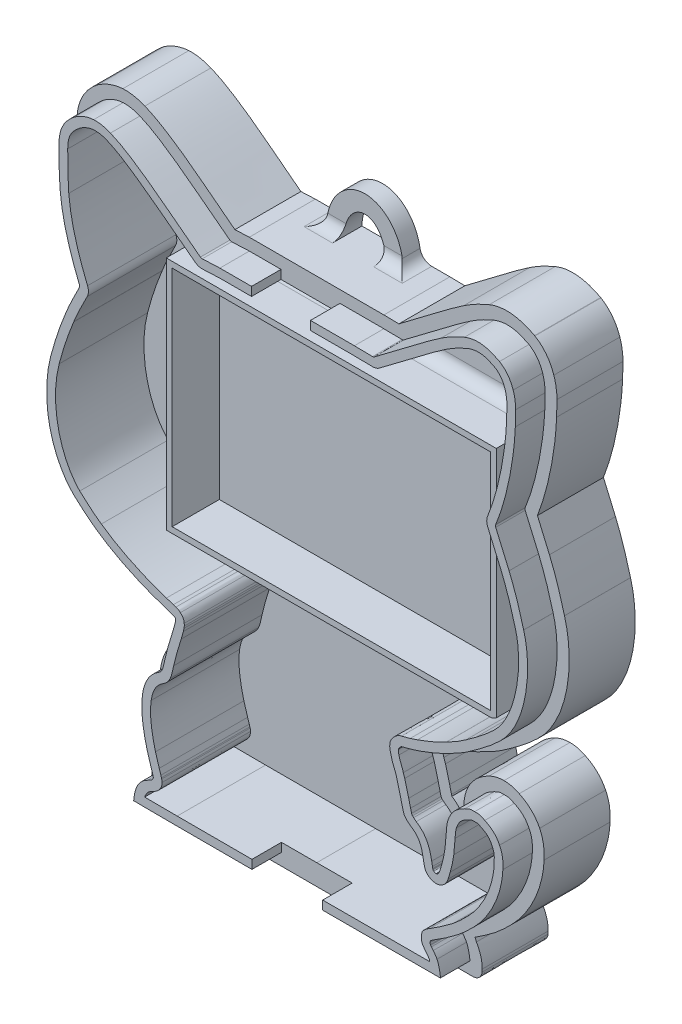
SolidWorks part; units mm, degrees
ref_plane "Front" through (0, 0, 0) normal (0, 0, 1) x (1, 0, 0)
ref_plane "Top" through (0, 0, 0) normal (0, 1, 0) x (1, 0, 0)
ref_plane "Right" through (0, 0, 0) normal (1, 0, 0) x (0, 0, -1)
sketch "Mech_Outlines_Dog" plane through (0, 0, 0) normal (0, 0, 1) x (1, 0, 0)
  line L1 (74.9398, 0.9126) -> (48.9706, 0.8869)
  line L7 (71.492, 32.5287) -> (70.2527, 32.1324)
  line L14 (63.42, 86.4697) -> (60.3508, 86.5232)
  line L15 (60.3508, 86.5232) -> (48.9353, 86.5232)
  line L16 (48.9353, 86.5232) -> (37.5273, 86.5232)
  line L17 (37.5273, 86.5232) -> (34.5339, 86.3884)
  line L22 (73.1431, 2.4109) -> (48.9672, 2.3716)
  line L27 (71.0247, 33.949) -> (69.8274, 33.5656)
  line L32 (63.3944, 84.986) -> (60.338, 85.0395)
  line L33 (60.338, 85.0395) -> (48.9354, 85.0395)
  line L34 (48.9354, 85.0395) -> (37.5613, 85.0395)
  line L35 (37.5613, 85.0395) -> (34.6011, 84.9061)
  line L40 (75.4762, -1.1182) -> (49.0458, -1.1447)
  line L42 (77.0346, 0.7654) -> (77.0108, 0.3114)
  line L48 (60.3548, 88.5576) -> (62.8985, 88.5136)
  line L51 (37.5165, 88.5576) -> (60.3548, 88.5576)
  line L53 (35.0717, 88.4472) -> (37.5165, 88.5576)
  line L56 (34.5113, 86.8831) -> (37.5166, 87.0182)
  line L57 (37.5166, 87.0182) -> (48.9356, 87.0182)
  line L58 (48.9356, 87.0182) -> (60.3546, 87.0182)
  line L59 (60.3546, 87.0182) -> (63.4286, 86.965)
  line L62 (70.4053, 31.6632) -> (71.6522, 32.0554)
  line L63 (75.4324, 0.8747) -> (75.3997, 0.419)
  line L64 (75.3997, 0.419) -> (48.9694, 0.3927)
  spline S0 degree 3 poles (16.1085, 97.6224) (15.1263, 97.5645) (14.0794, 97.2279) (12.9032, 96.4251) knots 0 0 0 0 1 1 1 1
  spline S1 degree 3 poles (12.9032, 96.4251) (10.8702, 94.8674) (10.2573, 93.2137) (10.2274, 91.1494) knots 0 0 0 0 1 1 1 1
  spline S2 degree 3 poles (10.2274, 91.1494) (10.1937, 88.8245) (10.2902, 85.9514) (10.4089, 84.5626) knots 0 0 0 0 1 1 1 1
  spline S3 degree 3 poles (10.4089, 84.5626) (10.8046, 79.9338) (12.2076, 75.8345) (13.7003, 72.1489) knots 0 0 0 0 1 1 1 1
  spline S4 degree 3 poles (13.7003, 72.1489) (13.7533, 72.018) (13.7479, 71.8706) (13.6854, 71.744) knots 0 0 0 0 1 1 1 1
  spline S5 degree 3 poles (13.6854, 71.744) (12.8695, 70.0922) (12.0156, 68.4848) (11.3692, 66.8103) knots 0 0 0 0 1 1 1 1
  spline S6 degree 3 poles (11.3692, 66.8103) (11.3675, 66.8062) (11.3657, 66.8022) (11.3638, 66.7981) knots 0 0 0 0 1 1 1 1
  spline S7 degree 3 poles (11.3638, 66.7981) (10.3632, 64.3951) (9.5104, 61.8412) (8.8174, 59.1813) knots 0 0 0 0 1 1 1 1
  spline S8 degree 3 poles (8.8174, 59.1813) (7.136, 52.6817) (8.6138, 44.9032) (12.7203, 40.814) knots 0 0 0 0 1 1 1 1
  spline S9 degree 3 poles (12.7203, 40.814) (13.8839, 39.7054) (15.1708, 38.6412) (16.5528, 37.6527) knots 0 0 0 0 1 1 1 1
  spline S10 degree 3 poles (16.5528, 37.6527) (19.588, 35.4818) (23.8433, 33.4143) (28.0129, 32.0933) knots 0 0 0 0 1 1 1 1
  spline S11 degree 3 poles (28.0129, 32.0933) (28.4457, 31.9562) (28.8478, 31.8228) (29.152, 31.7174) knots 0 0 0 0 1 1 1 1
  spline S12 degree 3 poles (29.152, 31.7174) (29.3041, 31.6647) (29.4314, 31.6193) (29.5293, 31.582) knots 0 0 0 0 1 1 1 1
  spline S13 degree 3 poles (29.5293, 31.582) (29.6997, 31.528) (29.7592, 31.4685) (29.8367, 31.4215) knots 0 0 0 0 1 1 1 1
  spline S14 degree 3 poles (29.8367, 31.4215) (30.0145, 31.2642) (29.9977, 31.1577) (30.0053, 31.0998) knots 0 0 0 0 1 1 1 1
  spline S15 degree 3 poles (30.0053, 31.0998) (30.013, 31.0418) (30.011, 31.008) (30.0094, 30.9765) knots 0 0 0 0 1 1 1 1
  spline S16 degree 3 poles (30.0094, 30.9765) (30.0062, 30.9135) (29.9984, 30.8639) (29.9884, 30.8065) knots 0 0 0 0 1 1 1 1
  spline S17 degree 3 poles (29.9884, 30.8065) (29.9685, 30.6918) (29.938, 30.5555) (29.897, 30.3921) knots 0 0 0 0 1 1 1 1
  spline S18 degree 3 poles (29.897, 30.3921) (29.815, 30.0653) (29.6927, 29.6377) (29.5475, 29.1758) knots 0 0 0 0 1 1 1 1
  spline S19 degree 3 poles (29.5475, 29.1758) (28.8677, 27.0124) (28.5655, 25.9343) (28.2351, 24.4934) knots 0 0 0 0 1 1 1 1
  spline S20 degree 3 poles (28.2351, 24.4934) (27.9956, 23.449) (27.9088, 22.9752) (27.7373, 22.5937) knots 0 0 0 0 1 1 1 1
  spline S21 degree 3 poles (27.7373, 22.5937) (27.6515, 22.403) (27.5225, 22.233) (27.3845, 22.1142) knots 0 0 0 0 1 1 1 1
  spline S22 degree 3 poles (27.3845, 22.1142) (27.2464, 21.9955) (27.1173, 21.9196) (26.9591, 21.8122) knots 0 0 0 0 1 1 1 1
  spline S23 degree 3 poles (26.9591, 21.8122) (25.5697, 20.8686) (24.7237, 19.4316) (24.4067, 17.4) knots 0 0 0 0 1 1 1 1
  spline S24 degree 3 poles (24.4067, 17.4) (24.0896, 15.3685) (24.3311, 12.7525) (25.1692, 9.5949) knots 0 0 0 0 1 1 1 1
  spline S25 degree 3 poles (25.1692, 9.5949) (25.3317, 8.9826) (25.6352, 7.9761) (25.8316, 7.3959) knots 0 0 0 0 1 1 1 1
  spline S26 degree 3 poles (25.8316, 7.3959) (25.9342, 7.0925) (26.0276, 6.8033) (26.0964, 6.5765) knots 0 0 0 0 1 1 1 1
  spline S27 degree 3 poles (26.0964, 6.5765) (26.1307, 6.4631) (26.1585, 6.3654) (26.1797, 6.2859) knots 0 0 0 0 1 1 1 1
  spline S28 degree 3 poles (26.1797, 6.2859) (26.1902, 6.2462) (26.1992, 6.2118) (26.2067, 6.1769) knots 0 0 0 0 1 1 1 1
  spline S29 degree 3 poles (26.2067, 6.1769) (26.2143, 6.142) (26.2257, 6.1318) (26.2257, 6.0245) knots 0 0 0 0 1 1 1 1
  spline S30 degree 3 poles (26.2257, 6.0245) (26.2257, 5.8348) (26.1568, 5.7565) (26.1167, 5.7015) knots 0 0 0 0 1 1 1 1
  spline S31 degree 3 poles (26.1167, 5.7015) (26.0766, 5.6465) (26.0428, 5.6144) (26.0097, 5.5843) knots 0 0 0 0 1 1 1 1
  spline S32 degree 3 poles (26.0097, 5.5843) (25.9433, 5.5242) (25.878, 5.4775) (25.8031, 5.4286) knots 0 0 0 0 1 1 1 1
  spline S33 degree 3 poles (25.8031, 5.4286) (25.6534, 5.3307) (25.4697, 5.2302) (25.2654, 5.1346) knots 0 0 0 0 1 1 1 1
  spline S34 degree 3 poles (25.2654, 5.1346) (24.0959, 4.5874) (23.3401, 3.5522) (23.0427, 1.9977) knots 0 0 0 0 1 1 1 1
  spline S35 degree 3 poles (23.0427, 1.9977) (22.964, 1.5861) (22.9165, 1.2157) (22.8985, 0.9548) knots 0 0 0 0 1 1 1 1
  spline S36 degree 3 poles (22.8985, 0.9548) (22.8982, 0.9505) (22.8987, 0.9495) (22.8985, 0.9453) knots 0 0 0 0 1 1 1 1
  spline S37 degree 3 poles (22.8985, 0.9453) (22.9412, 0.9442) (22.9602, 0.9428) (23.0095, 0.9418) knots 0 0 0 0 1 1 1 1
  spline S38 degree 3 poles (23.0095, 0.9418) (23.3672, 0.9341) (23.895, 0.9269) (24.5719, 0.9208) knots 0 0 0 0 1 1 1 1
  spline S39 degree 3 poles (24.5719, 0.9208) (25.9256, 0.9085) (27.8776, 0.8993) (30.281, 0.893) knots 0 0 0 0 1 1 1 1
  spline S40 degree 3 poles (30.281, 0.893) (35.0878, 0.8804) (41.7026, 0.8797) (48.9706, 0.8869) knots 0 0 0 0 1 1 1 1
  spline S41 degree 3 poles (74.9398, 0.9126) (74.9724, 1.3839) (74.669, 2.8108) (74.3757, 3.392) knots 0 0 0 0 1 1 1 1
  spline S42 degree 3 poles (74.3757, 3.392) (74.2334, 3.6739) (73.9, 4.1595) (73.7316, 4.3421) knots 0 0 0 0 1 1 1 1
  spline S43 degree 3 poles (73.7316, 4.3421) (73.6085, 4.4757) (73.4981, 4.6071) (73.4106, 4.7234) knots 0 0 0 0 1 1 1 1
  spline S44 degree 3 poles (73.4106, 4.7234) (73.3669, 4.7816) (73.329, 4.8348) (73.2941, 4.8927) knots 0 0 0 0 1 1 1 1
  spline S45 degree 3 poles (73.2941, 4.8927) (73.2767, 4.9217) (73.2598, 4.9511) (73.2413, 4.993) knots 0 0 0 0 1 1 1 1
  spline S46 degree 3 poles (73.2413, 4.993) (73.2228, 5.0349) (73.1905, 5.076) (73.1905, 5.2219) knots 0 0 0 0 1 1 1 1
  spline S47 degree 3 poles (73.1905, 5.2219) (73.1905, 5.5363) (73.3056, 5.5597) (73.3578, 5.616) knots 0 0 0 0 1 1 1 1
  spline S48 degree 3 poles (73.3578, 5.616) (73.41, 5.6724) (73.4583, 5.7124) (73.5122, 5.7542) knots 0 0 0 0 1 1 1 1
  spline S49 degree 3 poles (73.5122, 5.7542) (73.6199, 5.8378) (73.7464, 5.9196) (73.8881, 5.998) knots 0 0 0 0 1 1 1 1
  spline S50 degree 3 poles (73.8881, 5.998) (74.7385, 6.4683) (76.9394, 7.9781) (77.9813, 8.8146) knots 0 0 0 0 1 1 1 1
  spline S51 degree 3 poles (77.9813, 8.8146) (79.226, 9.8139) (80.8168, 11.3707) (81.637, 12.3836) knots 0 0 0 0 1 1 1 1
  spline S52 degree 3 poles (81.637, 12.3836) (84.0319, 15.3411) (85.3661, 18.6885) (85.5378, 22.1256) knots 0 0 0 0 1 1 1 1
  spline S53 degree 3 poles (85.5378, 22.1256) (85.6136, 23.643) (85.4812, 24.4092) (84.9811, 25.4434) knots 0 0 0 0 1 1 1 1
  spline S54 degree 3 poles (84.9811, 25.4434) (84.4438, 26.5544) (83.7351, 27.2385) (82.4747, 27.8394) knots 0 0 0 0 1 1 1 1
  spline S55 degree 3 poles (82.4747, 27.8394) (81.5208, 28.2943) (81.637, 28.2688) (80.7593, 28.2688) knots 0 0 0 0 1 1 1 1
  spline S56 degree 3 poles (80.7593, 28.2688) (79.8855, 28.2688) (79.9954, 28.293) (79.0797, 27.8543) knots 0 0 0 0 1 1 1 1
  spline S57 degree 3 poles (79.0797, 27.8543) (77.5705, 27.1313) (76.7543, 26.2458) (76.259, 24.8217) knots 0 0 0 0 1 1 1 1
  spline S58 degree 3 poles (76.259, 24.8217) (76.0847, 24.3204) (76.007, 23.8462) (75.938, 22.7575) knots 0 0 0 0 1 1 1 1
  spline S59 degree 3 poles (75.938, 22.7575) (75.8864, 21.9425) (75.7936, 20.8688) (75.7267, 20.3289) knots 0 0 0 0 1 1 1 1
  spline S60 degree 3 poles (75.7267, 20.3289) (75.6352, 19.5905) (75.4028, 18.5493) (75.1701, 17.6863) knots 0 0 0 0 1 1 1 1
  spline S61 degree 3 poles (75.1701, 17.6863) (75.0537, 17.2549) (74.9391, 16.8726) (74.8348, 16.5885) knots 0 0 0 0 1 1 1 1
  spline S62 degree 3 poles (74.8348, 16.5885) (74.7827, 16.4465) (74.7375, 16.3338) (74.6736, 16.2215) knots 0 0 0 0 1 1 1 1
  spline S63 degree 3 poles (74.6736, 16.2215) (74.6417, 16.1654) (74.6178, 16.1084) (74.5125, 16.0204) knots 0 0 0 0 1 1 1 1
  spline S64 degree 3 poles (74.5125, 16.0204) (74.4598, 15.9763) (74.3749, 15.9137) (74.226, 15.8984) knots 0 0 0 0 1 1 1 1
  spline S65 degree 3 poles (74.226, 15.8984) (74.0771, 15.8832) (73.8945, 15.9611) (73.8088, 16.0468) knots 0 0 0 0 1 1 1 1
  spline S66 degree 3 poles (73.8088, 16.0468) (73.6952, 16.1604) (73.7087, 16.1881) (73.6971, 16.2161) knots 0 0 0 0 1 1 1 1
  spline S67 degree 3 poles (73.6971, 16.2161) (73.6855, 16.244) (73.6793, 16.2621) (73.674, 16.2791) knots 0 0 0 0 1 1 1 1
  spline S68 degree 3 poles (73.674, 16.2791) (73.6635, 16.313) (73.6564, 16.3423) (73.6483, 16.3759) knots 0 0 0 0 1 1 1 1
  spline S69 degree 3 poles (73.6483, 16.3759) (73.6321, 16.4431) (73.6147, 16.5243) (73.5955, 16.6217) knots 0 0 0 0 1 1 1 1
  spline S70 degree 3 poles (73.5955, 16.6217) (73.5571, 16.8166) (73.512, 17.0723) (73.4675, 17.3484) knots 0 0 0 0 1 1 1 1
  spline S71 degree 3 poles (73.4675, 17.3484) (73.116, 19.5286) (72.2864, 20.9205) (70.8513, 21.8493) knots 0 0 0 0 1 1 1 1
  spline S72 degree 3 poles (70.8513, 21.8493) (70.681, 21.9596) (70.5241, 22.0799) (70.3929, 22.1988) knots 0 0 0 0 1 1 1 1
  spline S73 degree 3 poles (70.3929, 22.1988) (70.3273, 22.2582) (70.2681, 22.3165) (70.2134, 22.3816) knots 0 0 0 0 1 1 1 1
  spline S74 degree 3 poles (70.2134, 22.3816) (70.1586, 22.4467) (70.1012, 22.4987) (70.0536, 22.662) knots 0 0 0 0 1 1 1 1
  spline S75 degree 3 poles (70.0536, 22.662) (70.022, 22.77) (69.9713, 22.98) (69.8836, 23.3358) knots 0 0 0 0 1 1 1 1
  spline S76 degree 3 poles (69.8836, 23.3358) (69.7959, 23.6916) (69.6827, 24.1554) (69.5653, 24.6422) knots 0 0 0 0 1 1 1 1
  spline S77 degree 3 poles (69.5653, 24.6422) (69.3325, 25.607) (69.0226, 26.7879) (68.8928, 27.2143) knots 0 0 0 0 1 1 1 1
  spline S78 degree 3 poles (68.8928, 27.2143) (68.829, 27.4238) (68.7314, 27.6944) (68.6449, 27.943) knots 0 0 0 0 1 1 1 1
  spline S79 degree 3 poles (68.6449, 27.943) (68.4728, 28.6982) (68.1277, 29.2538) (67.902, 30.1603) knots 0 0 0 0 1 1 1 1
  spline S80 degree 3 poles (67.902, 30.1603) (67.8356, 30.4354) (67.788, 30.6996) (67.8519, 30.9947) knots 0 0 0 0 1 1 1 1
  spline S81 degree 3 poles (67.8519, 30.9947) (67.9158, 31.2897) (68.2169, 31.6162) (68.5562, 31.6746) knots 0 0 0 0 1 1 1 1
  spline S82 degree 3 poles (68.5562, 31.6746) (68.7453, 31.7047) (69.5821, 31.9215) (70.2527, 32.1324) knots 0 0 0 0 1 1 1 1
  spline S83 degree 3 poles (71.492, 32.5287) (73.2584, 33.1478) (74.9712, 33.8823) (76.6363, 34.7642) knots 0 0 0 0 1 1 1 1
  spline S84 degree 3 poles (76.6363, 34.7642) (76.639, 34.7656) (76.6421, 34.767) (76.6451, 34.7683) knots 0 0 0 0 1 1 1 1
  spline S85 degree 3 poles (76.6451, 34.7683) (78.05, 35.4763) (79.1164, 36.1165) (80.1477, 36.8684) knots 0 0 0 0 1 1 1 1
  spline S86 degree 3 poles (80.1477, 36.8684) (80.5017, 37.1265) (81.2678, 37.6841) (81.8523, 38.1077) knots 0 0 0 0 1 1 1 1
  spline S87 degree 3 poles (81.8523, 38.1077) (82.9542, 38.9064) (84.0321, 39.8115) (85.0441, 40.7815) knots 0 0 0 0 1 1 1 1
  spline S88 degree 3 poles (85.0441, 40.7815) (89.4404, 44.9023) (90.6758, 53.4557) (89.0723, 59.1176) knots 0 0 0 0 1 1 1 1
  spline S89 degree 3 poles (89.0723, 59.1176) (89.0713, 59.121) (89.0706, 59.1243) (89.0695, 59.1277) knots 0 0 0 0 1 1 1 1
  spline S90 degree 3 poles (89.0695, 59.1277) (88.3821, 61.7674) (87.5422, 64.3151) (86.5996, 66.5786) knots 0 0 0 0 1 1 1 1
  spline S91 degree 3 poles (86.5996, 66.5786) (85.9445, 68.1619) (85.0951, 70.1031) (84.3316, 71.8319) knots 0 0 0 0 1 1 1 1
  spline S92 degree 3 poles (84.3316, 71.8319) (84.277, 71.9552) (84.2751, 72.0953) (84.3262, 72.22) knots 0 0 0 0 1 1 1 1
  spline S93 degree 3 poles (84.3262, 72.22) (86.2256, 76.8323) (87.4523, 83.2033) (87.6568, 88.2549) knots 0 0 0 0 1 1 1 1
  spline S94 degree 3 poles (87.6568, 88.2549) (87.6933, 89.156) (87.7129, 90.0068) (87.7164, 90.806) knots 0 0 0 0 1 1 1 1
  spline S95 degree 3 poles (87.7164, 90.806) (87.7165, 91.2801) (87.6649, 92.3563) (87.2904, 93.4831) knots 0 0 0 0 1 1 1 1
  spline S96 degree 3 poles (87.2904, 93.4831) (86.9162, 94.609) (86.2349, 95.7695) (84.9729, 96.5191) knots 0 0 0 0 1 1 1 1
  spline S97 degree 3 poles (84.9729, 96.5191) (83.6571, 97.2286) (81.5853, 98.1604) (79.0153, 97.1117) knots 0 0 0 0 1 1 1 1
  spline S98 degree 3 poles (79.0153, 97.1117) (77.7563, 96.598) (76.3931, 95.8948) (75.0467, 94.9927) knots 0 0 0 0 1 1 1 1
  spline S99 degree 3 poles (75.0467, 94.9927) (71.9886, 92.9435) (67.928, 89.6189) (63.7193, 86.5645) knots 0 0 0 0 1 1 1 1
  spline S100 degree 3 poles (63.7193, 86.5645) (63.6325, 86.5012) (63.5274, 86.4679) (63.42, 86.4697) knots 0 0 0 0 1 1 1 1
  spline S101 degree 3 poles (34.5339, 86.3884) (34.4203, 86.3833) (34.3084, 86.4175) (34.217, 86.4853) knots 0 0 0 0 1 1 1 1
  spline S102 degree 3 poles (34.217, 86.4853) (29.3204, 90.1096) (23.1108, 95.3799) (18.9569, 97.08) knots 0 0 0 0 1 1 1 1
  spline S103 degree 3 poles (18.9569, 97.08) (18.0268, 97.4561) (17.0933, 97.6805) (16.1085, 97.6224) knots 0 0 0 0 1 1 1 1
  spline S104 degree 3 poles (16.1938, 96.1413) (15.4989, 96.1004) (14.7441, 95.8759) (13.7687, 95.2169) knots 0 0 0 0 1 1 1 1
  spline S105 degree 3 poles (13.7687, 95.2169) (12.0783, 93.9098) (11.7344, 92.871) (11.7092, 91.1291) knots 0 0 0 0 1 1 1 1
  spline S106 degree 3 poles (11.7092, 91.1291) (11.6763, 88.8622) (11.776, 85.976) (11.8859, 84.69) knots 0 0 0 0 1 1 1 1
  spline S107 degree 3 poles (11.8859, 84.69) (12.2626, 80.2837) (13.6038, 76.3379) (15.0744, 72.707) knots 0 0 0 0 1 1 1 1
  spline S108 degree 3 poles (15.0744, 72.707) (15.2863, 72.1834) (15.2643, 71.5942) (15.0141, 71.0877) knots 0 0 0 0 1 1 1 1
  spline S109 degree 3 poles (15.0141, 71.0877) (14.185, 69.4091) (13.3549, 67.84) (12.7515, 66.2767) knots 0 0 0 0 1 1 1 1
  spline S110 degree 3 poles (12.7515, 66.2767) (12.7453, 66.2605) (12.739, 66.2445) (12.7325, 66.2286) knots 0 0 0 0 1 1 1 1
  spline S111 degree 3 poles (12.7325, 66.2286) (11.7606, 63.8947) (10.9288, 61.4063) (10.2525, 58.8108) knots 0 0 0 0 1 1 1 1
  spline S112 degree 3 poles (10.2525, 58.8108) (8.6952, 52.7918) (10.1873, 45.4432) (13.7558, 41.878) knots 0 0 0 0 1 1 1 1
  spline S113 degree 3 poles (13.7558, 41.878) (14.8637, 40.8235) (16.0922, 39.8065) (17.4142, 38.8609) knots 0 0 0 0 1 1 1 1
  spline S114 degree 3 poles (17.4142, 38.8609) (20.2797, 36.8114) (24.4364, 34.7832) (28.4592, 33.5087) knots 0 0 0 0 1 1 1 1
  spline S115 degree 3 poles (28.4592, 33.5087) (28.903, 33.3681) (29.3143, 33.2323) (29.6362, 33.1207) knots 0 0 0 0 1 1 1 1
  spline S116 degree 3 poles (29.6362, 33.1207) (29.7972, 33.0649) (29.9337, 33.016) (30.0568, 32.969) knots 0 0 0 0 1 1 1 1
  spline S117 degree 3 poles (30.0568, 32.969) (30.6405, 32.7016) (30.339, 32.9545) (30.818, 32.5342) knots 0 0 0 0 1 1 1 1
  spline S118 degree 3 poles (30.818, 32.5342) (31.5202, 31.9131) (31.4475, 31.5028) (31.4749, 31.2955) knots 0 0 0 0 1 1 1 1
  spline S119 degree 3 poles (31.4749, 31.2955) (31.5024, 31.0883) (31.4942, 30.9868) (31.4898, 30.9014) knots 0 0 0 0 1 1 1 1
  spline S120 degree 3 poles (31.4898, 30.9014) (31.4811, 30.7305) (31.4648, 30.6433) (31.4492, 30.5533) knots 0 0 0 0 1 1 1 1
  spline S121 degree 3 poles (31.4492, 30.5533) (31.4179, 30.3732) (31.3803, 30.2159) (31.3341, 30.0318) knots 0 0 0 0 1 1 1 1
  spline S122 degree 3 poles (31.3341, 30.0318) (31.2416, 29.6635) (31.1141, 29.2167) (30.9616, 28.7315) knots 0 0 0 0 1 1 1 1
  spline S123 degree 3 poles (30.9616, 28.7315) (30.2864, 26.583) (30.002, 25.5679) (29.6796, 24.1622) knots 0 0 0 0 1 1 1 1
  spline S124 degree 3 poles (29.6796, 24.1622) (29.4419, 23.1257) (29.4009, 22.6792) (29.0891, 21.9856) knots 0 0 0 0 1 1 1 1
  spline S125 degree 3 poles (29.0891, 21.9856) (28.9331, 21.6388) (28.6202, 21.2223) (28.3502, 20.9901) knots 0 0 0 0 1 1 1 1
  spline S126 degree 3 poles (28.3502, 20.9901) (28.0802, 20.7578) (27.9259, 20.6757) (27.7915, 20.5844) knots 0 0 0 0 1 1 1 1
  spline S127 degree 3 poles (27.7915, 20.5844) (26.7593, 19.8835) (26.1415, 18.9015) (25.8715, 17.1718) knots 0 0 0 0 1 1 1 1
  spline S128 degree 3 poles (25.8715, 17.1718) (25.6015, 15.4421) (25.7971, 13.0078) (26.6016, 9.9769) knots 0 0 0 0 1 1 1 1
  spline S129 degree 3 poles (26.6016, 9.9769) (26.7505, 9.4157) (27.0568, 8.4004) (27.2355, 7.8727) knots 0 0 0 0 1 1 1 1
  spline S130 degree 3 poles (27.2355, 7.8727) (27.3428, 7.5557) (27.4394, 7.2555) (27.5145, 7.0079) knots 0 0 0 0 1 1 1 1
  spline S131 degree 3 poles (27.5145, 7.0079) (27.552, 6.8841) (27.5835, 6.7751) (27.612, 6.6679) knots 0 0 0 0 1 1 1 1
  spline S132 degree 3 poles (27.612, 6.6679) (27.6262, 6.6143) (27.6399, 6.5627) (27.6553, 6.4912) knots 0 0 0 0 1 1 1 1
  spline S133 degree 3 poles (27.6553, 6.4912) (27.6708, 6.4196) (27.7075, 6.4282) (27.7075, 6.0252) knots 0 0 0 0 1 1 1 1
  spline S134 degree 3 poles (27.7075, 6.0252) (27.7075, 5.2923) (27.4472, 5.0106) (27.314, 4.8279) knots 0 0 0 0 1 1 1 1
  spline S135 degree 3 poles (27.314, 4.8279) (27.1808, 4.6452) (27.0851, 4.5581) (27.0038, 4.4845) knots 0 0 0 0 1 1 1 1
  spline S136 degree 3 poles (27.0038, 4.4845) (26.8414, 4.3374) (26.7289, 4.2629) (26.6131, 4.1872) knots 0 0 0 0 1 1 1 1
  spline S137 degree 3 poles (26.6131, 4.1872) (26.3815, 4.0358) (26.1526, 3.9128) (25.8925, 3.791) knots 0 0 0 0 1 1 1 1
  spline S138 degree 3 poles (25.8925, 3.791) (25.3519, 3.538) (25.011, 3.0738) (24.7561, 2.4054) knots 0 0 0 0 1 1 1 1
  spline S139 degree 3 poles (24.7561, 2.4054) (26.098, 2.3937) (27.954, 2.3844) (30.283, 2.3783) knots 0 0 0 0 1 1 1 1
  spline S140 degree 3 poles (30.283, 2.3783) (35.0865, 2.3658) (41.7003, 2.3644) (48.9672, 2.3716) knots 0 0 0 0 1 1 1 1
  spline S141 degree 3 poles (73.1431, 2.4109) (73.1124, 2.5325) (73.0842, 2.6997) (73.0645, 2.7386) knots 0 0 0 0 1 1 1 1
  spline S142 degree 3 poles (73.0645, 2.7386) (72.8449, 3.1433) (72.4981, 3.5205) (72.2383, 3.8473) knots 0 0 0 0 1 1 1 1
  spline S143 degree 3 poles (72.2383, 3.8473) (72.1747, 3.9319) (72.1144, 4.0144) (72.0372, 4.1425) knots 0 0 0 0 1 1 1 1
  spline S144 degree 3 poles (72.0372, 4.1425) (71.9985, 4.2066) (71.9552, 4.279) (71.8977, 4.4094) knots 0 0 0 0 1 1 1 1
  spline S145 degree 3 poles (71.8977, 4.4094) (71.8401, 4.5398) (71.7209, 4.6745) (71.7209, 5.2376) knots 0 0 0 0 1 1 1 1
  spline S146 degree 3 poles (71.7209, 5.2376) (71.7209, 6.4544) (72.1416, 6.4876) (72.283, 6.6402) knots 0 0 0 0 1 1 1 1
  spline S147 degree 3 poles (72.283, 6.6402) (72.4244, 6.7928) (72.5209, 6.869) (72.6162, 6.9429) knots 0 0 0 0 1 1 1 1
  spline S148 degree 3 poles (72.6162, 6.9429) (72.8068, 7.0908) (72.9824, 7.201) (73.1844, 7.3127) knots 0 0 0 0 1 1 1 1
  spline S149 degree 3 poles (73.1844, 7.3127) (73.8246, 7.6667) (76.1327, 9.2382) (77.0663, 9.9878) knots 0 0 0 0 1 1 1 1
  spline S150 degree 3 poles (77.0663, 9.9878) (78.2095, 10.9055) (79.7957, 12.4662) (80.4979, 13.3333) knots 0 0 0 0 1 1 1 1
  spline S151 degree 3 poles (80.4979, 13.3333) (82.7172, 16.074) (83.9146, 19.1142) (84.0696, 22.2159) knots 0 0 0 0 1 1 1 1
  spline S152 degree 3 poles (84.0696, 22.2159) (84.1391, 23.608) (84.0692, 23.9653) (83.6592, 24.8131) knots 0 0 0 0 1 1 1 1
  spline S153 degree 3 poles (83.6592, 24.8131) (83.2508, 25.6575) (82.8926, 26.0183) (81.8496, 26.5156) knots 0 0 0 0 1 1 1 1
  spline S154 degree 3 poles (81.8496, 26.5156) (81.404, 26.7167) (81.6277, 26.8014) (80.7735, 26.8014) knots 0 0 0 0 1 1 1 1
  spline S155 degree 3 poles (80.7735, 26.8014) (79.9242, 26.8014) (80.2197, 26.7515) (79.7353, 26.5326) knots 0 0 0 0 1 1 1 1
  spline S156 degree 3 poles (79.7353, 26.5326) (78.4713, 25.9612) (78.0585, 25.4528) (77.6751, 24.3505) knots 0 0 0 0 1 1 1 1
  spline S157 degree 3 poles (77.6751, 24.3505) (77.5544, 24.0033) (77.4994, 23.7229) (77.4334, 22.6798) knots 0 0 0 0 1 1 1 1
  spline S158 degree 3 poles (77.4334, 22.6798) (77.3798, 21.8337) (77.2901, 20.778) (77.214, 20.1632) knots 0 0 0 0 1 1 1 1
  spline S159 degree 3 poles (77.214, 20.1632) (77.105, 19.2836) (76.865, 18.2328) (76.618, 17.3168) knots 0 0 0 0 1 1 1 1
  spline S160 degree 3 poles (76.618, 17.3168) (76.4945, 16.8587) (76.374, 16.4531) (76.2421, 16.0937) knots 0 0 0 0 1 1 1 1
  spline S161 degree 3 poles (76.2421, 16.0937) (76.1762, 15.914) (76.1262, 15.7639) (75.9787, 15.5045) knots 0 0 0 0 1 1 1 1
  spline S162 degree 3 poles (75.9787, 15.5045) (75.9049, 15.3748) (75.8576, 15.2148) (75.4789, 14.8984) knots 0 0 0 0 1 1 1 1
  spline S163 degree 3 poles (75.4789, 14.8984) (75.2895, 14.7402) (74.9692, 14.4978) (74.3919, 14.4385) knots 0 0 0 0 1 1 1 1
  spline S164 degree 3 poles (74.3919, 14.4385) (73.8146, 14.3792) (73.1017, 14.6865) (72.774, 15.0142) knots 0 0 0 0 1 1 1 1
  spline S165 degree 3 poles (72.774, 15.0142) (72.324, 15.4641) (72.381, 15.5658) (72.3406, 15.663) knots 0 0 0 0 1 1 1 1
  spline S166 degree 3 poles (72.3406, 15.663) (72.3001, 15.7602) (72.2851, 15.8107) (72.2715, 15.8546) knots 0 0 0 0 1 1 1 1
  spline S167 degree 3 poles (72.2715, 15.8546) (72.2442, 15.9424) (72.2318, 15.9928) (72.2194, 16.0443) knots 0 0 0 0 1 1 1 1
  spline S168 degree 3 poles (72.2194, 16.0443) (72.1945, 16.1472) (72.1753, 16.2414) (72.1537, 16.351) knots 0 0 0 0 1 1 1 1
  spline S169 degree 3 poles (72.1537, 16.351) (72.1104, 16.5703) (72.0631, 16.8376) (72.0162, 17.1285) knots 0 0 0 0 1 1 1 1
  spline S170 degree 3 poles (72.0162, 17.1285) (71.7093, 19.0315) (71.1304, 19.9262) (70.059, 20.6196) knots 0 0 0 0 1 1 1 1
  spline S171 degree 3 poles (70.059, 20.6196) (69.8204, 20.7741) (69.6132, 20.9315) (69.4102, 21.1154) knots 0 0 0 0 1 1 1 1
  spline S172 degree 3 poles (69.4102, 21.1154) (69.3087, 21.2073) (69.2094, 21.3029) (69.0919, 21.4425) knots 0 0 0 0 1 1 1 1
  spline S173 degree 3 poles (69.0919, 21.4425) (68.9745, 21.582) (68.8106, 21.6882) (68.6429, 22.2626) knots 0 0 0 0 1 1 1 1
  spline S174 degree 3 poles (68.6429, 22.2626) (68.5625, 22.538) (68.545, 22.6375) (68.4566, 22.9961) knots 0 0 0 0 1 1 1 1
  spline S175 degree 3 poles (68.4566, 22.9961) (68.3682, 23.355) (68.2543, 23.8209) (68.1363, 24.3099) knots 0 0 0 0 1 1 1 1
  spline S176 degree 3 poles (68.1363, 24.3099) (67.9088, 25.2527) (67.5877, 26.4666) (67.4868, 26.798) knots 0 0 0 0 1 1 1 1
  spline S177 degree 3 poles (67.4868, 26.798) (67.441, 26.9485) (67.3481, 27.21) (67.2573, 27.4712) knots 0 0 0 0 1 1 1 1
  spline S178 degree 3 poles (67.2573, 27.4712) (66.9209, 28.4482) (66.9, 28.1075) (66.4737, 29.828) knots 0 0 0 0 1 1 1 1
  spline S179 degree 3 poles (66.4737, 29.828) (66.3826, 30.2052) (66.2637, 30.623) (66.4155, 31.324) knots 0 0 0 0 1 1 1 1
  spline S180 degree 3 poles (66.4155, 31.324) (66.5672, 32.025) (67.4922, 33.0109) (68.3185, 33.1532) knots 0 0 0 0 1 1 1 1
  spline S181 degree 3 poles (68.3185, 33.1532) (68.3268, 33.1546) (68.3352, 33.156) (68.3436, 33.1573) knots 0 0 0 0 1 1 1 1
  spline S182 degree 3 poles (68.3436, 33.1573) (68.2419, 33.1411) (69.2025, 33.3691) (69.8274, 33.5656) knots 0 0 0 0 1 1 1 1
  spline S183 degree 3 poles (71.0247, 33.949) (72.7235, 34.545) (74.3625, 35.248) (75.9529, 36.0904) knots 0 0 0 0 1 1 1 1
  spline S184 degree 3 poles (75.9529, 36.0904) (75.9648, 36.0968) (75.9768, 36.1031) (75.9888, 36.1093) knots 0 0 0 0 1 1 1 1
  spline S185 degree 3 poles (75.9888, 36.1093) (77.3417, 36.7911) (78.3228, 37.3819) (79.2843, 38.0828) knots 0 0 0 0 1 1 1 1
  spline S186 degree 3 poles (79.2843, 38.0828) (79.6409, 38.3428) (80.4071, 38.8996) (80.9929, 39.3242) knots 0 0 0 0 1 1 1 1
  spline S187 degree 3 poles (80.9929, 39.3242) (82.0357, 40.08) (83.0639, 40.9435) (84.029, 41.8685) knots 0 0 0 0 1 1 1 1
  spline S189 degree 3 poles (84.029, 41.8685) (87.797, 45.4005) (89.0902, 53.6089) (87.6433, 58.7174) knots 0 0 0 0 1 1 1 1
  spline S190 degree 3 poles (87.6433, 58.7174) (87.6396, 58.7309) (87.636, 58.7445) (87.6325, 58.7581) knots 0 0 0 0 1 1 1 1
  spline S191 degree 3 poles (87.6325, 58.7581) (86.9607, 61.3378) (86.1393, 63.8249) (85.2284, 66.0126) knots 0 0 0 0 1 1 1 1
  spline S192 degree 3 poles (85.2284, 66.0126) (84.5826, 67.5731) (83.7358, 69.508) (82.9738, 71.2334) knots 0 0 0 0 1 1 1 1
  spline S193 degree 3 poles (82.9738, 71.2334) (82.7558, 71.7269) (82.7487, 72.2881) (82.9542, 72.787) knots 0 0 0 0 1 1 1 1
  spline S194 degree 3 poles (82.9542, 72.787) (84.7571, 77.1647) (85.9768, 83.4515) (86.1738, 88.3159) knots 0 0 0 0 1 1 1 1
  spline S195 degree 3 poles (86.1738, 88.3159) (86.2095, 89.1989) (86.2292, 90.0306) (86.2327, 90.8081) knots 0 0 0 0 1 1 1 1
  spline S196 degree 3 poles (86.2327, 90.8081) (86.2327, 91.1814) (86.181, 92.1145) (85.8819, 93.0146) knots 0 0 0 0 1 1 1 1
  spline S197 degree 3 poles (85.8819, 93.0146) (85.5839, 93.9112) (85.1, 94.7112) (84.2234, 95.2359) knots 0 0 0 0 1 1 1 1
  spline S198 degree 3 poles (84.2234, 95.2359) (83.0241, 95.8803) (81.5688, 96.5501) (79.5762, 95.7371) knots 0 0 0 0 1 1 1 1
  spline S199 degree 3 poles (79.5762, 95.7371) (78.4083, 95.2605) (77.1307, 94.6023) (75.8731, 93.7595) knots 0 0 0 0 1 1 1 1
  spline S200 degree 3 poles (75.8731, 93.7595) (72.9259, 91.7847) (68.8472, 88.4521) (64.591, 85.3632) knots 0 0 0 0 1 1 1 1
  spline S201 degree 3 poles (64.591, 85.3632) (64.2436, 85.111) (63.8236, 84.9786) (63.3944, 84.986) knots 0 0 0 0 1 1 1 1
  spline S202 degree 3 poles (34.6011, 84.9061) (34.1469, 84.8854) (33.6995, 85.0217) (33.334, 85.2921) knots 0 0 0 0 1 1 1 1
  spline S203 degree 3 poles (33.334, 85.2921) (28.3627, 88.9715) (22.0502, 94.2093) (18.3962, 95.7052) knots 0 0 0 0 1 1 1 1
  spline S204 degree 3 poles (18.3962, 95.7052) (17.598, 96.0277) (16.8978, 96.1828) (16.1938, 96.1413) knots 0 0 0 0 1 1 1 1
  spline S205 degree 3 poles (16.0611, 99.6528) (14.6917, 99.572) (13.2477, 99.079) (11.8148, 98.0978) knots 0 0 0 0 1 1 1 1
  spline S206 degree 3 poles (11.8148, 98.0978) (11.7928, 98.0826) (11.7711, 98.0668) (11.7498, 98.0504) knots 0 0 0 0 1 1 1 1
  spline S207 degree 3 poles (11.7498, 98.0504) (9.2878, 96.1693) (8.3016, 93.6701) (8.2655, 91.1792) knots 0 0 0 0 1 1 1 1
  spline S208 degree 3 poles (8.2655, 91.1792) (8.2306, 88.7748) (8.3237, 85.9188) (8.4544, 84.3893) knots 0 0 0 0 1 1 1 1
  spline S209 degree 3 poles (8.4544, 84.3893) (8.8524, 79.7334) (10.2049, 75.652) (11.6354, 72.0447) knots 0 0 0 0 1 1 1 1
  spline S210 degree 3 poles (11.6354, 72.0447) (10.9212, 70.619) (10.1679, 69.1565) (9.5495, 67.5573) knots 0 0 0 0 1 1 1 1
  spline S211 degree 3 poles (9.5495, 67.5573) (8.514, 65.0675) (7.6345, 62.4324) (6.9212, 59.6939) knots 0 0 0 0 1 1 1 1
  spline S212 degree 3 poles (6.9212, 59.6939) (5.0707, 52.5417) (6.5251, 44.1835) (11.3618, 39.3708) knots 0 0 0 0 1 1 1 1
  spline S213 degree 3 poles (11.3618, 39.3708) (11.3694, 39.3631) (11.377, 39.3554) (11.3848, 39.3478) knots 0 0 0 0 1 1 1 1
  spline S214 degree 3 poles (11.3848, 39.3478) (12.6215, 38.169) (13.9827, 37.0447) (15.4421, 36.0009) knots 0 0 0 0 1 1 1 1
  spline S215 degree 3 poles (15.4421, 36.0009) (18.71, 33.6636) (23.1001, 31.5412) (27.4711, 30.1564) knots 0 0 0 0 1 1 1 1
  spline S216 degree 3 poles (27.4711, 30.1564) (27.5813, 30.1215) (27.6534, 30.0955) (27.7583, 30.0616) knots 0 0 0 0 1 1 1 1
  spline S217 degree 3 poles (27.7583, 30.0616) (27.7278, 29.9601) (27.7132, 29.8953) (27.6797, 29.7887) knots 0 0 0 0 1 1 1 1
  spline S218 degree 3 poles (27.6797, 29.7887) (26.9935, 27.605) (26.6668, 26.4399) (26.3252, 24.9505) knots 0 0 0 0 1 1 1 1
  spline S219 degree 3 poles (26.3252, 24.9505) (26.1044, 23.9876) (25.9955, 23.6101) (25.988, 23.5635) knots 0 0 0 0 1 1 1 1
  spline S220 degree 3 poles (25.988, 23.5635) (25.9453, 23.5339) (25.9675, 23.5506) (25.8898, 23.4978) knots 0 0 0 0 1 1 1 1
  spline S221 degree 3 poles (25.8898, 23.4978) (24.0106, 22.2217) (22.8514, 20.1616) (22.4698, 17.7163) knots 0 0 0 0 1 1 1 1
  spline S222 degree 3 poles (22.4698, 17.7163) (22.0881, 15.271) (22.3921, 12.4074) (23.2763, 9.0762) knots 0 0 0 0 1 1 1 1
  spline S223 degree 3 poles (23.2763, 9.0762) (23.4575, 8.3938) (23.7572, 7.3986) (23.978, 6.7465) knots 0 0 0 0 1 1 1 1
  spline S224 degree 3 poles (23.978, 6.7465) (23.987, 6.7197) (23.9921, 6.7018) (24.001, 6.6754) knots 0 0 0 0 1 1 1 1
  spline S225 degree 3 poles (24.001, 6.6754) (22.4988, 5.7713) (21.4695, 4.2232) (21.1173, 2.3824) knots 0 0 0 0 1 1 1 1
  spline S226 degree 3 poles (21.1173, 2.3824) (21.0249, 1.8994) (20.9675, 1.4678) (20.9419, 1.0977) knots 0 0 0 0 1 1 1 1
  spline S227 degree 3 poles (20.9419, 1.0977) (20.9292, 0.9126) (20.9226, 0.7479) (20.9331, 0.5559) knots 0 0 0 0 1 1 1 1
  spline S228 degree 3 poles (20.9331, 0.5559) (20.9384, 0.4599) (20.945, 0.3593) (20.9785, 0.2051) knots 0 0 0 0 1 1 1 1
  spline S229 degree 3 poles (20.9785, 0.2051) (21.012, 0.0508) (20.9807, -0.1756) (21.4173, -0.6123) knots 0 0 0 0 1 1 1 1
  spline S230 degree 3 poles (21.4173, -0.6123) (21.4176, -0.6126) (21.7791, -0.8855) (21.8765, -0.9293) knots 0 0 0 0 1 1 1 1
  spline S231 degree 3 poles (21.8765, -0.9293) (21.9739, -0.9731) (22.0342, -0.9912) (22.0824, -1.0051) knots 0 0 0 0 1 1 1 1
  spline S232 degree 3 poles (22.0824, -1.0051) (22.1788, -1.033) (22.2254, -1.0393) (22.2639, -1.0458) knots 0 0 0 0 1 1 1 1
  spline S233 degree 3 poles (22.2639, -1.0458) (22.3408, -1.0587) (22.3753, -1.0617) (22.4095, -1.0647) knots 0 0 0 0 1 1 1 1
  spline S234 degree 3 poles (22.4095, -1.0647) (22.4778, -1.0709) (22.5274, -1.0729) (22.5869, -1.0756) knots 0 0 0 0 1 1 1 1
  spline S235 degree 3 poles (22.5869, -1.0756) (22.7059, -1.081) (22.8521, -1.0851) (23.0393, -1.0891) knots 0 0 0 0 1 1 1 1
  spline S236 degree 3 poles (23.0393, -1.0891) (23.4137, -1.0972) (23.9456, -1.1046) (24.6267, -1.1108) knots 0 0 0 0 1 1 1 1
  spline S237 degree 3 poles (24.6267, -1.1108) (25.9891, -1.1232) (27.943, -1.1323) (30.3487, -1.1386) knots 0 0 0 0 1 1 1 1
  spline S238 degree 3 poles (30.3487, -1.1386) (35.16, -1.1512) (41.7763, -1.1519) (49.0458, -1.1447) knots 0 0 0 0 1 1 1 1
  spline S239 degree 3 poles (75.4762, -1.1182) (76.2834, -1.1176) (76.953, -0.4937) (77.0108, 0.3114) knots 0 0 0 0 1 1 1 1
  spline S240 degree 3 poles (77.0346, 0.7654) (77.0544, 2.054) (76.6753, 3.1912) (76.0582, 4.2601) knots 0 0 0 0 1 1 1 1
  spline S241 degree 3 poles (76.0582, 4.2601) (75.9987, 4.4666) (75.8808, 4.6452) (75.8052, 4.8394) knots 0 0 0 0 1 1 1 1
  spline S242 degree 3 poles (75.8052, 4.8394) (76.9391, 5.5555) (78.298, 6.4929) (79.2246, 7.2368) knots 0 0 0 0 1 1 1 1
  spline S243 degree 3 poles (79.2246, 7.2368) (80.6087, 8.3479) (82.2065, 9.8993) (83.1884, 11.1119) knots 0 0 0 0 1 1 1 1
  spline S244 degree 3 poles (83.1884, 11.1119) (85.824, 14.3666) (87.3457, 18.1368) (87.5403, 22.0336) knots 0 0 0 0 1 1 1 1
  spline S245 degree 3 poles (87.5403, 22.0336) (87.6247, 23.7229) (87.4069, 25.0485) (86.7832, 26.3381) knots 0 0 0 0 1 1 1 1
  spline S246 degree 3 poles (86.7832, 26.3381) (86.0692, 27.8146) (84.8783, 28.942) (83.3198, 29.685) knots 0 0 0 0 1 1 1 1
  spline S247 degree 3 poles (83.3198, 29.685) (82.3462, 30.1493) (81.6393, 30.3128) (80.7294, 30.3128) knots 0 0 0 0 1 1 1 1
  spline S248 degree 3 poles (80.7294, 30.3128) (79.822, 30.3128) (79.1096, 30.1483) (78.1708, 29.6986) knots 0 0 0 0 1 1 1 1
  spline S249 degree 3 poles (78.1708, 29.6986) (76.3077, 28.806) (74.9565, 27.365) (74.3079, 25.4997) knots 0 0 0 0 1 1 1 1
  spline S250 degree 3 poles (74.3079, 25.4997) (74.0601, 24.7873) (73.9507, 24.047) (73.8778, 22.8958) knots 0 0 0 0 1 1 1 1
  spline S251 degree 3 poles (73.8778, 22.8958) (73.8536, 22.5131) (73.8157, 22.1751) (73.779, 21.7526) knots 0 0 0 0 1 1 1 1
  spline S252 degree 3 poles (73.779, 21.7526) (73.2615, 22.4545) (72.6676, 23.0874) (71.9267, 23.5669) knots 0 0 0 0 1 1 1 1
  spline S253 degree 3 poles (71.9267, 23.5669) (71.9114, 23.5768) (71.9031, 23.5857) (71.8874, 23.5967) knots 0 0 0 0 1 1 1 1
  spline S254 degree 3 poles (71.8874, 23.5967) (71.8588, 23.7085) (71.863, 23.6916) (71.8285, 23.8317) knots 0 0 0 0 1 1 1 1
  spline S255 degree 3 poles (71.8285, 23.8317) (71.7419, 24.1832) (71.6297, 24.6448) (71.5129, 25.1286) knots 0 0 0 0 1 1 1 1
  spline S256 degree 3 poles (71.5129, 25.1286) (71.2729, 26.1236) (70.9787, 27.2598) (70.8093, 27.8165) knots 0 0 0 0 1 1 1 1
  spline S257 degree 3 poles (70.8093, 27.8165) (70.721, 28.1067) (70.6175, 28.3897) (70.537, 28.6211) knots 0 0 0 0 1 1 1 1
  spline S258 degree 3 poles (70.537, 28.6211) (70.3612, 29.2041) (70.4875, 28.7393) (70.3583, 29.2157) knots 0 0 0 0 1 1 1 1
  spline S259 degree 3 poles (70.3583, 29.2157) (70.2427, 29.5318) (70.1768, 29.7331) (70.0792, 30.0013) knots 0 0 0 0 1 1 1 1
  spline S260 degree 3 poles (70.0792, 30.0013) (70.3394, 30.0767) (70.5587, 30.1142) (70.8391, 30.2024) knots 0 0 0 0 1 1 1 1
  spline S261 degree 3 poles (70.8391, 30.2024) (71.2685, 30.3372) (71.709, 30.4754) (72.134, 30.6108) knots 0 0 0 0 1 1 1 1
  spline S262 degree 3 poles (72.134, 30.6108) (73.9823, 31.2586) (75.7854, 32.0315) (77.543, 32.9615) knots 0 0 0 0 1 1 1 1
  spline S263 degree 3 poles (77.543, 32.9615) (79.0124, 33.7027) (80.1912, 34.4079) (81.3145, 35.2268) knots 0 0 0 0 1 1 1 1
  spline S264 degree 3 poles (81.3145, 35.2268) (81.665, 35.4823) (82.4324, 36.0398) (83.0151, 36.4621) knots 0 0 0 0 1 1 1 1
  spline S265 degree 3 poles (83.0151, 36.4621) (84.1962, 37.3182) (85.3407, 38.2808) (86.4155, 39.3105) knots 0 0 0 0 1 1 1 1
  spline S266 degree 3 poles (86.4155, 39.3105) (91.6653, 44.2388) (92.8188, 53.2558) (91.003, 59.6729) knots 0 0 0 0 1 1 1 1
  spline S267 degree 3 poles (91.003, 59.6729) (91.0027, 59.6743) (91.0028, 59.676) (91.0024, 59.6777) knots 0 0 0 0 1 1 1 1
  spline S268 degree 3 poles (91.0024, 59.6777) (90.2954, 62.3869) (89.4333, 65.0062) (88.4519, 67.3636) knots 0 0 0 0 1 1 1 1
  spline S269 degree 3 poles (88.4519, 67.3636) (87.8543, 68.8077) (87.1052, 70.5159) (86.4066, 72.1015) knots 0 0 0 0 1 1 1 1
  spline S270 degree 3 poles (86.4066, 72.1015) (88.2916, 76.9502) (89.4561, 83.0888) (89.6621, 88.1784) knots 0 0 0 0 1 1 1 1
  spline S271 degree 3 poles (89.6621, 88.1784) (89.6995, 89.1021) (89.7201, 89.9782) (89.7237, 90.8054) knots 0 0 0 0 1 1 1 1
  spline S272 degree 3 poles (89.7237, 90.8054) (89.7239, 91.4182) (89.6718, 92.6874) (89.1941, 94.1245) knots 0 0 0 0 1 1 1 1
  spline S273 degree 3 poles (89.1941, 94.1245) (88.7165, 95.5616) (87.7646, 97.2144) (85.9793, 98.2725) knots 0 0 0 0 1 1 1 1
  spline S274 degree 3 poles (85.9793, 98.2725) (85.9617, 98.2828) (85.9438, 98.2928) (85.9258, 98.3023) knots 0 0 0 0 1 1 1 1
  spline S275 degree 3 poles (85.9258, 98.3023) (84.4659, 99.0907) (81.5573, 100.3571) (78.2196, 98.9951) knots 0 0 0 0 1 1 1 1
  spline S276 degree 3 poles (78.2196, 98.9951) (76.8356, 98.4304) (75.3552, 97.6667) (73.8873, 96.6831) knots 0 0 0 0 1 1 1 1
  spline S277 degree 3 poles (73.8873, 96.6831) (70.7836, 94.6033) (66.8969, 91.4391) (62.8985, 88.5136) knots 0 0 0 0 1 1 1 1
  spline S280 degree 3 poles (35.0717, 88.4472) (30.3417, 91.9893) (24.5032, 97.0386) (19.7947, 98.9647) knots 0 0 0 0 1 1 1 1
  spline S281 degree 3 poles (19.7947, 98.9647) (18.6845, 99.4139) (17.4308, 99.7335) (16.0611, 99.6528) knots 0 0 0 0 1 1 1 1
  spline S282 degree 3 poles (22.5543, 2.0915) (22.8743, 3.7639) (23.7352, 4.9669) (25.0536, 5.5838) knots 0 0 0 0 1 1 1 1
  spline S283 degree 3 poles (25.0536, 5.5838) (25.4249, 5.7576) (25.7287, 5.9564) (25.7287, 6.0256) knots 0 0 0 0 1 1 1 1
  spline S284 degree 3 poles (25.7287, 6.0256) (25.7287, 6.0948) (25.5632, 6.6404) (25.3609, 7.238) knots 0 0 0 0 1 1 1 1
  spline S285 degree 3 poles (25.3609, 7.238) (25.1586, 7.8357) (24.8564, 8.8396) (24.6894, 9.469) knots 0 0 0 0 1 1 1 1
  spline S286 degree 3 poles (24.6894, 9.469) (22.9907, 15.8686) (23.6624, 20.1728) (26.6795, 22.2217) knots 0 0 0 0 1 1 1 1
  spline S287 degree 3 poles (26.6795, 22.2217) (27.344, 22.6729) (27.2709, 22.5103) (27.7511, 24.6043) knots 0 0 0 0 1 1 1 1
  spline S288 degree 3 poles (27.7511, 24.6043) (28.0842, 26.057) (28.3922, 27.1563) (29.0736, 29.3246) knots 0 0 0 0 1 1 1 1
  spline S289 degree 3 poles (29.0736, 29.3246) (29.3591, 30.233) (29.5542, 31.0103) (29.5071, 31.0519) knots 0 0 0 0 1 1 1 1
  spline S290 degree 3 poles (29.5071, 31.0519) (29.4601, 31.0936) (28.7194, 31.3501) (27.8612, 31.622) knots 0 0 0 0 1 1 1 1
  spline S291 degree 3 poles (27.8612, 31.622) (23.6426, 32.9585) (19.3544, 35.0396) (16.2626, 37.251) knots 0 0 0 0 1 1 1 1
  spline S292 degree 3 poles (16.2626, 37.251) (14.8605, 38.2539) (13.5547, 39.3338) (12.3724, 40.4607) knots 0 0 0 0 1 1 1 1
  spline S293 degree 3 poles (12.3724, 40.4607) (8.0865, 44.7253) (6.6138, 52.6467) (8.3368, 59.3063) knots 0 0 0 0 1 1 1 1
  spline S294 degree 3 poles (8.3368, 59.3063) (9.0353, 61.9873) (9.8952, 64.5636) (10.9053, 66.9894) knots 0 0 0 0 1 1 1 1
  spline S295 degree 3 poles (10.9053, 66.9894) (11.5659, 68.7009) (12.4282, 70.3216) (13.2396, 71.9644) knots 0 0 0 0 1 1 1 1
  spline S296 degree 3 poles (13.2396, 71.9644) (11.7395, 75.6682) (10.3159, 79.8187) (9.9139, 84.5216) knots 0 0 0 0 1 1 1 1
  spline S297 degree 3 poles (9.9139, 84.5216) (9.7923, 85.9446) (9.6966, 88.8136) (9.7305, 91.1579) knots 0 0 0 0 1 1 1 1
  spline S298 degree 3 poles (9.7305, 91.1579) (9.762, 93.3288) (10.4659, 95.1894) (12.6101, 96.8277) knots 0 0 0 0 1 1 1 1
  spline S299 degree 3 poles (12.6101, 96.8277) (15.0948, 98.5292) (17.1938, 98.3272) (19.1427, 97.5385) knots 0 0 0 0 1 1 1 1
  spline S300 degree 3 poles (19.1427, 97.5385) (23.4634, 95.771) (29.639, 90.4894) (34.5113, 86.8831) knots 0 0 0 0 1 1 1 1
  spline S301 degree 3 poles (63.4286, 86.965) (67.6214, 90.0079) (71.6762, 93.3299) (74.7714, 95.4039) knots 0 0 0 0 1 1 1 1
  spline S302 degree 3 poles (74.7714, 95.4039) (76.1473, 96.3258) (77.5392, 97.0431) (78.8286, 97.5693) knots 0 0 0 0 1 1 1 1
  spline S303 degree 3 poles (78.8286, 97.5693) (81.5912, 98.6966) (83.8713, 97.6769) (85.2217, 96.9477) knots 0 0 0 0 1 1 1 1
  spline S304 degree 3 poles (85.2217, 96.9477) (88.0045, 95.2985) (88.2116, 91.8206) (88.2114, 90.8053) knots 0 0 0 0 1 1 1 1
  spline S305 degree 3 poles (88.2114, 90.8053) (88.2079, 89.9989) (88.1879, 89.1408) (88.1512, 88.2336) knots 0 0 0 0 1 1 1 1
  spline S306 degree 3 poles (88.1512, 88.2336) (87.9441, 83.1197) (86.7154, 76.7219) (84.7838, 72.0315) knots 0 0 0 0 1 1 1 1
  spline S307 degree 3 poles (84.7838, 72.0315) (85.5478, 70.3015) (86.3982, 68.3577) (87.0565, 66.7668) knots 0 0 0 0 1 1 1 1
  spline S308 degree 3 poles (87.0565, 66.7668) (88.0096, 64.478) (88.8563, 61.9098) (89.5489, 59.2502) knots 0 0 0 0 1 1 1 1
  spline S309 degree 3 poles (89.5489, 59.2502) (91.2047, 53.4038) (89.9888, 44.7358) (85.3831, 40.4187) knots 0 0 0 0 1 1 1 1
  spline S310 degree 3 poles (85.3831, 40.4187) (84.3555, 39.4337) (83.2613, 38.5137) (82.1396, 37.7007) knots 0 0 0 0 1 1 1 1
  spline S311 degree 3 poles (82.1396, 37.7007) (81.5556, 37.2774) (80.7888, 36.7204) (80.4357, 36.4629) knots 0 0 0 0 1 1 1 1
  spline S312 degree 3 poles (80.4357, 36.4629) (79.3811, 35.6941) (78.2868, 35.0378) (76.8646, 34.3211) knots 0 0 0 0 1 1 1 1
  spline S313 degree 3 poles (76.8646, 34.3211) (75.1759, 33.4267) (73.4397, 32.6819) (71.6522, 32.0554) knots 0 0 0 0 1 1 1 1
  spline S314 degree 3 poles (70.4053, 31.6632) (69.7195, 31.4475) (68.9243, 31.2338) (68.6382, 31.1884) knots 0 0 0 0 1 1 1 1
  spline S315 degree 3 poles (68.6382, 31.1884) (67.9304, 31.0665) (68.5596, 29.7193) (68.94, 28.679) knots 0 0 0 0 1 1 1 1
  spline S316 degree 3 poles (68.94, 28.679) (69.0369, 28.4617) (69.2248, 27.8183) (69.3642, 27.3601) knots 0 0 0 0 1 1 1 1
  spline S317 degree 3 poles (69.3642, 27.3601) (69.5037, 26.9019) (69.8097, 25.7317) (70.0443, 24.7595) knots 0 0 0 0 1 1 1 1
  spline S318 degree 3 poles (70.0443, 24.7595) (70.2788, 23.7874) (70.4956, 22.9068) (70.526, 22.8027) knots 0 0 0 0 1 1 1 1
  spline S319 degree 3 poles (70.526, 22.8027) (70.5564, 22.6986) (70.8228, 22.457) (71.1181, 22.266) knots 0 0 0 0 1 1 1 1
  spline S320 degree 3 poles (71.1181, 22.266) (72.6744, 21.2587) (73.5873, 19.7014) (73.9538, 17.4287) knots 0 0 0 0 1 1 1 1
  spline S321 degree 3 poles (73.9538, 17.4287) (74.0412, 16.8863) (74.1326, 16.4227) (74.1568, 16.3985) knots 0 0 0 0 1 1 1 1
  spline S322 degree 3 poles (74.1568, 16.3985) (74.3156, 16.2397) (75.0624, 19.0086) (75.2337, 20.3914) knots 0 0 0 0 1 1 1 1
  spline S323 degree 3 poles (75.2337, 20.3914) (75.2975, 20.9063) (75.3914, 21.9859) (75.4424, 22.7904) knots 0 0 0 0 1 1 1 1
  spline S324 degree 3 poles (75.4424, 22.7904) (75.5123, 23.8944) (75.5975, 24.4329) (75.7897, 24.9855) knots 0 0 0 0 1 1 1 1
  spline S325 degree 3 poles (75.7897, 24.9855) (76.3222, 26.5169) (77.2683, 27.5376) (78.8636, 28.3018) knots 0 0 0 0 1 1 1 1
  spline S326 degree 3 poles (78.8636, 28.3018) (79.7849, 28.7432) (79.875, 28.7652) (80.7569, 28.7652) knots 0 0 0 0 1 1 1 1
  spline S327 degree 3 poles (80.7569, 28.7652) (81.6424, 28.7652) (81.7267, 28.7444) (82.6855, 28.2872) knots 0 0 0 0 1 1 1 1
  spline S328 degree 3 poles (82.6855, 28.2872) (84.0184, 27.6517) (84.8444, 26.8593) (85.4246, 25.6593) knots 0 0 0 0 1 1 1 1
  spline S329 degree 3 poles (85.4246, 25.6593) (85.9548, 24.563) (86.1083, 23.6615) (86.0304, 22.1023) knots 0 0 0 0 1 1 1 1
  spline S330 degree 3 poles (86.0304, 22.1023) (85.8531, 18.5534) (84.4733, 15.1028) (82.0199, 12.0731) knots 0 0 0 0 1 1 1 1
  spline S331 degree 3 poles (82.0199, 12.0731) (81.1603, 11.0116) (79.5673, 9.456) (78.2886, 8.4295) knots 0 0 0 0 1 1 1 1
  spline S332 degree 3 poles (78.2886, 8.4295) (77.2107, 7.564) (75.046, 6.0753) (74.1255, 5.5662) knots 0 0 0 0 1 1 1 1
  spline S333 degree 3 poles (74.1255, 5.5662) (73.8823, 5.4318) (73.6834, 5.2771) (73.6834, 5.2225) knots 0 0 0 0 1 1 1 1
  spline S334 degree 3 poles (73.6834, 5.2225) (73.6834, 5.1679) (73.8679, 4.923) (74.0935, 4.6783) knots 0 0 0 0 1 1 1 1
  spline S335 degree 3 poles (74.0935, 4.6783) (74.3191, 4.4335) (74.644, 3.9554) (74.8154, 3.6158) knots 0 0 0 0 1 1 1 1
  spline S336 degree 3 poles (74.8154, 3.6158) (75.173, 2.9074) (75.4802, 1.5425) (75.4324, 0.8747) knots 0 0 0 0 1 1 1 1
  spline S337 degree 3 poles (48.9694, 0.3927) (34.4327, 0.3783) (22.5078, 0.3978) (22.4315, 0.4741) knots 0 0 0 0 1 1 1 1
  spline S338 degree 3 poles (22.4315, 0.4741) (22.3552, 0.5504) (22.3902, 1.2336) (22.5543, 2.0915) knots 0 0 0 0 1 1 1 1
extrude "Boss-Extrude1" add sketch "Mech_Outlines_Dog" along normal blind 1.2 contours S203 S204 S104 S105 S106 S107 S108 S109 S110 S111 S112 S113 S114 S115 S116 S117 S118 S119 S120 S121 S122 S123 S124 S125 S126 S127 S128 S129 S130 S131 S132 S133 S134 S135 S136 S137 S138 S139 S140 L22 S141 S142 S143 S144 S145 S146 S147 S148 S149 S150 S151 | S102 S103 S0 S1 S2 S3 S4 S5 S6 S7 S8 S9 S10 S11 S12 S13 S14 S15 S16 S17 S18 S19 S20 S21 S22 S23 S24 S25 S26 S27 S28 S29 S30 S31 S32 S33 S34 S35 S36 S37 S38 S39 S40 L1 S41 S42 S43 S44 S45 S46 S47 | S338 S337 L64 L63 S336 S335 S334 S333 S332 S331 S330 S329 S328 S327 S326 S325 S324 S323 S322 S321 S320 S319 S318 S317 S316 S315 S314 L62 S313 S312 S311 S310 S309 S308 S307 S306 S305 S304 S303 S302 S301 L59 L58 L57 L56 S300 S299 S298 S297 S296 S295 | S280 S281 S205 S206 S207 S208 S209 S210 S211 S212 S213 S214 S215 S216 S217 S218 S219 S220 S221 S222 S223 S224 S225 S226 S227 S228 S229 S230 S231 S232 S233 S234 S235 S236 S237 S238 L40 S239 L42 S240 S241 S242 S243 S244 S245 S246 S247 S248 S249 S250 S251 region at (61.9539, 2.1655, 0) region at (49.6133, 50.2441, 0) region at (62.2596, 0.1915, 0) region at (36.0197, 86.8228, 0)
extrude "Boss-Extrude3" add sketch "Mech_Outlines_Dog<5>" along normal offset from surface (16.2 mm away) 15 contours S102 S103 S0 S1 S2 S3 S4 S5 S6 S7 S8 S9 S10 S11 S12 S13 S14 S15 S16 S17 S18 S19 S20 S21 S22 S23 S24 S25 S26 S27 S28 S29 S30 S31 S32 S33 S34 S35 S36 S37 S38 S39 S40 L1 S41 S42 S43 S44 S45 S46 S47 region at (61.9539, 2.1655, 0) up to face at (51.3507, 37.6405, 1.2) offset beyond the face yes
sketch "Mech_Outlines_Dog<5>" plane through (0, 0, 0) normal (0, 0, 1) x (1, 0, 0) same geometry as "Mech_Outlines_Dog"
extrude "Boss-Extrude2" add sketch "Mech_Outlines_Dog<4>" along direction (0, 0, 1) on the side of the normal offset from surface (11.2 mm away) 5 contours S280 S281 S205 S206 S207 S208 S209 S210 S211 S212 S213 S214 S215 S216 S217 S218 S219 S220 S221 S222 S223 S224 S225 S226 S227 S228 S229 S230 S231 S232 S233 S234 S235 S236 S237 S238 L40 S239 L42 S240 S241 S242 S243 S244 S245 S246 S247 S248 S249 S250 S251 | S338 S337 L64 L63 S336 S335 S334 S333 S332 S331 S330 S329 S328 S327 S326 S325 S324 S323 S322 S321 S320 S319 S318 S317 S316 S315 S314 L62 S313 S312 S311 S310 S309 S308 S307 S306 S305 S304 S303 S302 S301 L59 L58 L57 L56 S300 S299 S298 S297 S296 S295 region at (62.2596, 0.1915, 0) region at (36.0197, 86.8228, 0) up to face at (55.2086, 35.617, 16.2)
sketch "Mech_Outlines_Dog<4>" plane through (0, 0, 0) normal (0, 0, 1) x (1, 0, 0) same geometry as "Mech_Outlines_Dog"
sketch "Sketch1" plane through (0, 0, 16.2) normal (0, 0, 1) x (1, 0, 0)
  line L1 (42.9706, 3.3869) -> (54.9706, 3.3869)
  line L2 (42.9706, 3.3869) -> (42.9706, -0.6131)
  line L3 (42.9706, -0.6131) -> (54.9706, -0.6131)
  line L4 (54.9706, 3.3869) -> (54.9706, -0.6131)
  dimension "D1" = 6
  dimension "D2" = 6
  dimension "D3" = 4
  dimension "D4" = 2.5
extrude "Cut-Extrude2" cut sketch "Sketch1" against normal up to surface (5 mm away) up to face at (54.1066, 34.2484, 11.2)
sketch "Sketch2" plane through (0, 0, 16.2) normal (0, 0, 1) x (1, 0, 0)
  line L0 (60.3508, 86.5232) -> (37.5273, 86.5232) construction
  line L1 (42.8985, 91.5232) -> (52.8985, 91.5232)
  line L2 (42.8985, 91.5232) -> (42.8985, 80.0395)
  line L3 (42.8985, 80.0395) -> (52.8985, 80.0395)
  line L4 (52.8985, 91.5232) -> (52.8985, 80.0395)
  line L5 (37.5613, 85.0395) -> (60.338, 85.0395) construction
  point P4 (47.8985, 91.5232)
  dimension "D1" = 10
  dimension "D2" = 25
  dimension "D3" = 5
  dimension "D4" = 5
extrude "Cut-Extrude3" cut sketch "Sketch2" against normal up to surface (5 mm away) up to face at (53.9248, 33.1069, 11.2)
sketch "Sketch3" plane through (0, 0, 0) normal (0, 0, -1) x (-1, 0, 0)
  line L0 (-37.5165, 88.5576) -> (-60.3548, 88.5576) construction
  line L1 (-42.4866, 87.5576) -> (-45.5064, 87.5576)
  line L2 (-52.3649, 87.5576) -> (-55.3847, 87.5576)
  line L3 (-37.5165, 88.5576) -> (-60.3548, 88.5576) construction
  ellipse E0 centre (-48.9357, 88.5576) end of major axis (-48.9357, 93.5576) minor radius 3.5 (-45.5064, 87.5576) -> (-52.3649, 87.5576) ccw
  ellipse E1 centre (-48.9357, 88.5576) end of major axis (-48.9357, 96.5576) minor radius 6.5 (-42.4866, 87.5576) -> (-55.3847, 87.5576) ccw
  dimension "D1" = 7
  dimension "D2" = 5
  dimension "D3" = 3
  dimension "D4" = 3
  dimension "D5" = 1
extrude "Boss-Extrude4" add sketch "Sketch3" against normal blind 3
fillet "Fillet1" radius 2 4 edges at (55.4357, 88.5576, 1.5) (42.4357, 88.5576, 1.5) (53.9357, 88.5576, 3) (43.9357, 88.5576, 3)
sketch "Sketch4" plane through (0, 0, 1.2) normal (0, 0, 1) x (1, 0, 0)
  line L1 (22.4315, 37.4741) -> (76.4315, 37.4741)
  line L2 (22.4315, 37.4741) -> (22.4315, 75.4741)
  line L3 (22.4315, 75.4741) -> (76.4315, 75.4741)
  line L4 (76.4315, 37.4741) -> (76.4315, 75.4741)
  line L5 (22.4315, 37.4741) -> (76.4315, 75.4741) construction
  line L6 (22.4315, 75.4741) -> (76.4315, 37.4741) construction
  line L7 (21.4315, 36.4741) -> (77.4315, 36.4741)
  line L8 (21.4315, 36.4741) -> (21.4315, 76.4741)
  line L9 (21.4315, 76.4741) -> (77.4315, 76.4741)
  line L10 (77.4315, 36.4741) -> (77.4315, 76.4741)
  line L11 (21.4315, 36.4741) -> (77.4315, 76.4741) construction
  line L12 (21.4315, 76.4741) -> (77.4315, 36.4741) construction
  point P0 (49.4315, 56.4741)
  point P5 (49.4315, 56.4741)
  dimension "D1" = 27
  dimension "D2" = 56
  dimension "D3" = 54
  dimension "D4" = 38
  dimension "D5" = 1
  dimension "D6" = 1
extrude "Boss-Extrude5" add sketch "Sketch4" along normal blind 8
fillet "Fillet2" radius 2 4 edges at (21.4315, 56.4741, 1.2) (49.4315, 76.4741, 1.2) (77.4315, 56.6782, 1.2) (49.0624, 36.4741, 1.2)
